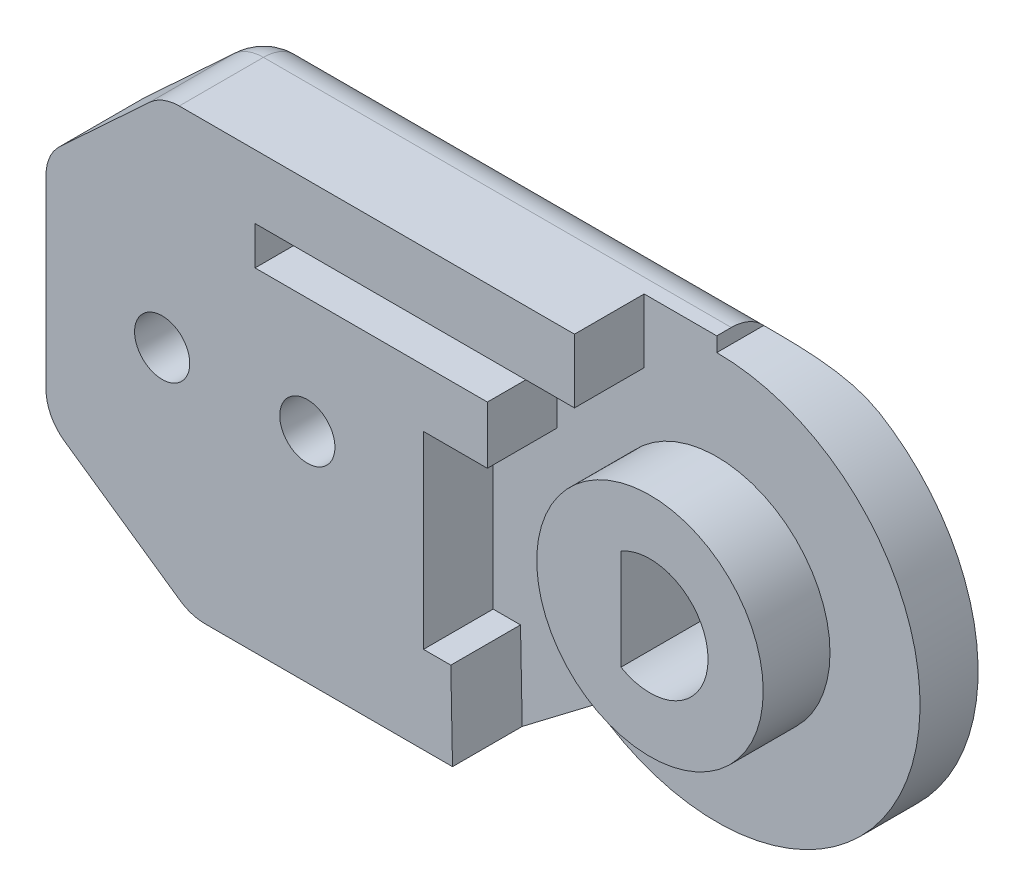
SolidWorks part; units mm, degrees
ref_plane "Front Plane" through (0, 0, 0) normal (0, 0, 1) x (1, 0, 0)
ref_plane "Top Plane" through (0, 0, 0) normal (0, 1, 0) x (1, 0, 0)
ref_plane "Right Plane" through (0, 0, 0) normal (1, 0, 0) x (0, 0, -1)
sketch "Sketch2" plane through (0, 0, 0) normal (0, 0, 1) x (1, 0, 0)
  line L1 (-2.5, 7.5) -> (-16.7, 7.5)
  line L2 (-20.7, 3.7934) -> (-20.7, -4.0316)
  line L3 (-15.7, -7.5) -> (-6.7, -7.5)
  line L4 (-6.7, -7.5) -> (-4.2, -5.6)
  line L5 (-2.5, 7.5) -> (0, 7.5)
  line L7 (0, 7) -> (0, 7.5)
  line L8 (-20.7, 3.7934) -> (-16.7, 7.5)
  line L9 (-20.7, -4.0316) -> (-15.7, -7.5)
  arc A1 (-4.2, -5.6) -> (7, 0) centre (0, 0) ccw
  arc A2 (7, 0) -> (0, 7) centre (0, 0) ccw
  dimension "D1" = 7
  dimension "D2" = 4
  dimension "D3" = 5
  dimension "D4" = 7.5
  dimension "D5" = 15
  dimension "D7" = 2.5
  dimension "D8" = 14
extrude "Boss-Extrude1" add sketch "Sketch2" along normal blind 2 contours A1 A2 L7 L5 L1 L8 L2 L9 L3 L4
sketch "Sketch4" plane through (0, 0, 2) normal (0, 0, 1) x (1, 0, 0)
  line L7 (-15.7, -7.5) -> (-6.7, -7.5)
  line L8 (-6.7, -7.5) -> (-6.7591, -4.5)
  line L9 (-6.7591, -4.5) -> (-7.7, -4.5)
  line L10 (-16.7, 7.5) -> (-2.5, 7.5)
  line L13 (-5.5, 2) -> (-5.5, 5.3)
  line L14 (-5.5, 5.3) -> (-2.5, 5.3)
  line L21 (-20.7, -4.0316) -> (-15.7, -7.5)
  line L24 (-16.7, 7.5) -> (-20.7, 3.7934)
  line L25 (-20.7, -4.0316) -> (-20.7, 3.7934)
  line L26 (-7.7, 2) -> (-5.5, 2)
  line L29 (-7.7, 2) -> (-7.7, -4.5)
  line L30 (-2.5, 7.5) -> (-2.5, 5.3)
  point P2 (-5.5, 3.65)
  dimension "D1" = 13
  dimension "D2" = 2.5
  dimension "D3" = 3
  dimension "D4" = 3
extrude "Boss-Extrude2" add sketch "Sketch4" along normal blind 6
ref_point "Point1"
sketch "Sketch22" plane through (0, 0, 2) normal (0, 0, 1) x (1, 0, 0)
  line L0 (0, 5.3) -> (-14, 5.3) construction
  line L1 (0, 4) -> (-14, 4) construction
  line L2 (-14, 4) -> (-14, 5.3) construction
  circle A0 centre (0, 0) radius 5.3 construction
  circle A1 centre (0, 0) radius 4 construction
  dimension "D1" = 14
  dimension "D2" = 10.6
  dimension "D3" = 8
sketch "Sketch24" plane through (0, 0, 2) normal (0, 0, 1) x (1, 0, 0)
  circle A0 centre (0, 0) radius 3.9
  dimension "D1" = 7.8
extrude "Boss-Extrude5" add sketch "Sketch24" along normal blind 2.3
sketch "Sketch29" plane through (-5.5, 0, 0) normal (1, 0, 0) x (0, 0, -1)
  line L0 (-1.9279, 3.9758) -> (-8, 3.9758) construction
  line L1 (-8, 2) -> (-8, 5.3) construction
sketch "Sketch30" plane through (-5.5, 0, 0) normal (1, 0, 0) x (0, 0, -1)
  line L0 (-4.4659, 3.9758) -> (-4.4659, 5.3)
  line L1 (-4.4659, 3.9758) -> (-2.0573, 3.9758)
  line L2 (-4.4659, 5.3) -> (-2.0573, 5.3)
  line L3 (-2.0573, 3.9758) -> (-2.0573, 5.3)
  line L4 (-1.9279, 3.9758) -> (-8, 3.9758) construction
  line L5 (-8, 5.3) -> (-2, 5.3) construction
extrude "Cut-Extrude12" cut sketch "Sketch30" against normal blind 8
ref_plane "Plane1" through (0, 0, 8) normal (0, 0, 1) x (1, 0, 0)
sketch "Sketch8" plane through (0, 0, 2) normal (0, 0, 1) x (1, 0, 0)
  circle A1 centre (0, 0) radius 3.8
  circle A2 centre (0, 0) radius 2.5
sketch "Sketch28" plane through (0, 0, 4.3) normal (0, 0, 1) x (1, 0, 0)
  line L0 (-1, 1.7321) -> (-1, -1.7321)
  arc A0 (-1, -1.7321) -> (-1, 1.7321) centre (0, 0) ccw
  dimension "D1" = 1
  dimension "D2" = 2
extrude "Cut-Extrude11" cut sketch "Sketch28" against normal through all
sketch "Sketch33" plane through (0, 0, 8) normal (0, 0, 1) x (1, 0, 0)
  line L0 (-7, 2) -> (-0.5657, -5.1566) construction
  line L2 (-8.2591, -4.5) -> (-2.6001, 3.0469) construction
  point P2 (0, 0)
  point P8 (0, 0)
  dimension "D1" = 1.5
  dimension "D2" = 1.5
fillet "Fillet1" radius 1.5 9 edges at (-11.2, -7.5, 0) (-8.35, 7.5, 0) (-18.7, 5.6467, 0) (-18.2, -5.7658, 0) (-20.7, -0.1191, 0) (-15.7, -7.5, 4) (-20.7, -4.0316, 4) (-20.7, 3.7934, 4) (-16.7, 7.5, 4)
sketch "Sketch34" plane through (0, 2, 0) normal (0, -1, 0) x (1, 0, 0)
  line L0 (-5.5, 1.9279) -> (-5.5, 8) construction
  circle A0 centre (-7, 8) radius 0.75
  point P3 (0, 0)
  dimension "D1" = 1.5
  dimension "D2" = 1.5
extrude "Cut-Extrude13" cut sketch "Sketch34" along direction (0.6686, -0.7436, 0) on the side against the normal blind 8
sketch "Sketch35" plane through (0, -4.5, 0) normal (0, 1, 0) x (1, 0, 0)
  circle A0 centre (-8.2591, -8) radius 0.75
extrude "Cut-Extrude14" cut sketch "Sketch35" along direction (0.5999, 0.8001, 0) on the side against the normal blind 8 and the other way blind 3
sketch "Sketch36" plane through (0, 0, 8) normal (0, 0, 1) x (1, 0, 0)
  line L2 (-7.7, -2.7542) -> (-7.7, 2) construction
  circle A0 centre (-11.7, 0) radius 0.95
  circle A1 centre (-16.7, 0) radius 0.95
  dimension "D1" = 4
  dimension "D2" = 5
extrude "Cut-Extrude15" cut sketch "Sketch36" against normal blind 8
sketch "Sketch37" plane through (0, 0, 0) normal (0, 0, -1) x (-1, 0, 0)
  circle A0 centre (11.7, 0) radius 2
  circle A1 centre (16.7, 0) radius 2
extrude "Cut-Extrude16" cut sketch "Sketch37" against normal blind 2.5
sketch "Sketch38" plane through (0, 0, 8) normal (0, 0, 1) x (1, 0, 0)
  line L0 (-5.5, 5.3) -> (-2.5, 5.3)
  line L1 (-5.5, 5.3) -> (-5.5, 6.55)
  line L2 (-2.5, 5.3) -> (-2.5, 6.55)
  line L3 (-5.5, 6.55) -> (-2.5, 6.55)
  dimension "D1" = 1.25
extrude "Cut-Extrude17" cut sketch "Sketch38" against normal blind 3.6
ref_plane "Plane2" through (0, 0, 4.4) normal (0, 0, 1) x (1, 0, 0)
split "Split1" trim tools "Plane2" bodies to split 129 resulting bodies 130 131
delete or keep bodies "Body-Delete/Keep 1" type delete bodies bodies 130
